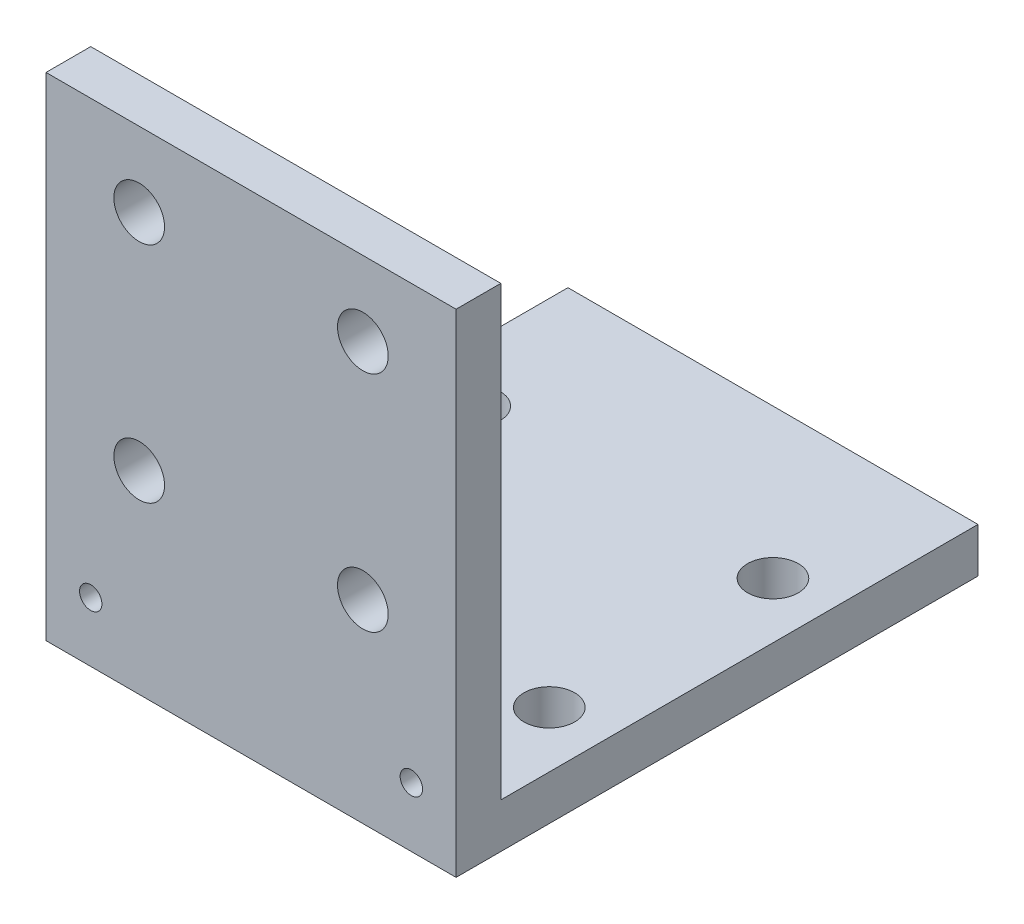
SolidWorks part; units mm, degrees
ref_plane "Front Plane" through (0, 0, 0) normal (0, 0, 1) x (1, 0, 0)
ref_plane "Top Plane" through (0, 0, 0) normal (0, 1, 0) x (1, 0, 0)
ref_plane "Right Plane" through (0, 0, 0) normal (1, 0, 0) x (0, 0, -1)
sketch "Sketch1" plane through (0, 0, 0) normal (0, 0, 1) x (1, 0, 0)
  line L1 (-13.75, 1.5) -> (13.75, 1.5)
  line L2 (-13.75, 1.5) -> (-13.75, -1.5)
  line L3 (-13.75, -1.5) -> (13.75, -1.5)
  line L4 (13.75, 1.5) -> (13.75, -1.5)
  line L5 (-13.75, 1.5) -> (13.75, -1.5) construction
  line L6 (-13.75, -1.5) -> (13.75, 1.5) construction
  point P0 (0, 0)
  dimension "D1" = 27.5
  dimension "D2" = 3
extrude "Boss-Extrude1" add sketch "Sketch1" along normal blind 35
sketch "Sketch2" plane through (0, 1.5, 0) normal (0, 1, 0) x (1, 0, 0)
  line L0 (-13.75, -32) -> (13.75, -32)
  line L1 (-13.75, -35) -> (-13.75, 0) construction
  line L2 (13.75, -35) -> (13.75, 0) construction
  line L3 (13.75, -35) -> (-13.75, -35) construction
  line L4 (13.75, -35) -> (-13.75, -35)
  line L5 (13.75, -35) -> (13.75, 0)
  line L6 (-13.75, -35) -> (-13.75, 0)
  line M3 (-13.75, 0) -> (-13.75, -35)
  line M4 (-13.75, -35) -> (13.75, -35)
  line M5 (13.75, -35) -> (13.75, 0)
  dimension "D1" = 3
extrude "Boss-Extrude2" add sketch "Sketch2" along normal blind 40 contours L0 M3 M4 M5 region at (0, 1.5, 33.5)
sketch "Sketch3" plane through (0, 1.5, 0) normal (0, 1, 0) x (1, 0, 0)
  line L0 (13.75, -35) -> (13.75, 0) construction
  line L1 (13.75, -35) -> (13.75, 0)
  line L6 (-13.75, 0) -> (-13.75, -32)
  line L7 (-13.75, -32) -> (13.75, -32)
  line L8 (13.75, -32) -> (13.75, 0)
  line L9 (13.75, 0) -> (-13.75, 0)
  line L10 (-13.75, 0) -> (-13.75, -32)
  line L11 (-13.75, -32) -> (13.75, -32)
  line L12 (13.75, -32) -> (13.75, 0)
  line L13 (13.75, 0) -> (-13.75, 0)
  circle A0 centre (10, -25) radius 1.7
  circle A1 centre (10, -10) radius 1.7
  circle A2 centre (-10, -10) radius 1.7
  circle A3 centre (-10, -25) radius 1.7
  point P8 (0, -17.5)
  point P11 (0, -17.5)
  dimension "D1" = 0
hole_wizard "M3 Clearance Hole1" positions "Sketch4" profile "Sketch5" hole size "M3" standard "ISO"
sketch "Sketch4" plane through (0, 1.5, 0) normal (0, 1, 0) x (1, 0, 0)
  point P0 (-10, -10)
  point P3 (-10, -25)
  point P6 (10, -25)
  point P9 (10, -10)
sketch "Sketch5" plane through (-10, 1.5, 10) normal (1, 0, 0) x (0, 0, 1)
  line L0 (0, 0) -> (0, 6.0215)
  line L1 (0, 6.0215) -> (1.7, 5)
  line L2 (1.7, 5) -> (1.7, 0)
  line L5 (1.7, 0) -> (0, 0)
  line L10 (0, 6.0215) -> (-1.7, 5) construction
  line L11 (0, -6.35) -> (0, 107.95) construction
  dimension "Hole Dia." = 3.4
  dimension "Hole Depth" = 5
  dimension "Drill Angle" = 118
sketch "Sketch6" plane through (0, 0, 35) normal (0, 0, 1) x (1, 0, 0)
  line L0 (-13.75, 41.5) -> (-13.75, -1.5) construction
  line L1 (-13.75, -1.5) -> (13.75, -1.5) construction
  circle A0 centre (-10.75, 2.5) radius 0.75
  dimension "D1" = 1.5
  dimension "D2" = 3
  dimension "D3" = 4
extrude "Cut-Extrude1" cut sketch "Sketch6" against normal blind 10
hole_wizard "M3 Clearance Hole2" positions "Sketch9" profile "Sketch10" hole size "M3" standard "ISO"
sketch "Sketch9" plane through (0, 0, 32) normal (0, 0, -1) x (-1, 0, 0)
  line L0 (13.75, 1.5) -> (-13.75, 1.5) construction
  point P0 (-7.5, 11.5)
  point P2 (7.5, 11.5)
  point P4 (7.5, 26.5)
  point P6 (-7.5, 26.5)
  point P17 (0, 1.5)
  dimension "D1" = 15
  dimension "D2" = 15
  dimension "D3" = 7.5
  dimension "D4" = 7.5
  dimension "D5" = 7.5
  dimension "D6" = 7.5
  dimension "D7" = 10
  dimension "D8" = 10
sketch "Sketch10" plane through (7.5, 11.5, 32) normal (1, 0, 0) x (0, 1, 0)
  line L0 (0, 0) -> (0, 6.0215)
  line L1 (0, 6.0215) -> (1.7, 5)
  line L2 (1.7, 5) -> (1.7, 0)
  line L5 (1.7, 0) -> (0, 0)
  line L10 (0, 6.0215) -> (-1.7, 5) construction
  line L11 (0, -6.35) -> (0, 107.95) construction
  dimension "Hole Dia." = 3.4
  dimension "Hole Depth" = 5
  dimension "Drill Angle" = 118
sketch "Sketch11" plane through (0, 0, 35) normal (0, 0, 1) x (1, 0, 0)
  line L4 (13.75, -1.5) -> (13.75, 41.5)
  line L5 (13.75, 41.5) -> (-13.75, 41.5)
  line L6 (-13.75, 41.5) -> (-13.75, -1.5)
  line L7 (-13.75, -1.5) -> (13.75, -1.5)
  line L8 (13.75, -1.5) -> (13.75, 41.5)
  line L9 (13.75, 41.5) -> (-13.75, 41.5)
  line L10 (-13.75, 41.5) -> (-13.75, -1.5)
  line L11 (-13.75, -1.5) -> (13.75, -1.5)
  circle A0 centre (7.5, 11.5) radius 1.7 construction
  circle A1 centre (7.5, 26.5) radius 1.7 construction
  circle A2 centre (-7.5, 26.5) radius 1.7 construction
  circle A3 centre (-7.5, 11.5) radius 1.7 construction
  circle A4 centre (7.5, 11.5) radius 1.7
  circle A5 centre (7.5, 26.5) radius 1.7
  circle A6 centre (-7.5, 26.5) radius 1.7
  circle A7 centre (-7.5, 11.5) radius 1.7
  dimension "D1" = 0
mirror "Mirror1" about plane through (0, 0, 0) normal (1, 0, 0) of "Cut-Extrude1"
sketch "Sketch12" plane through (0, 0, 32) normal (0, 0, -1) x (-1, 0, 0)
  line L0 (-13.75, 31.5) -> (13.75, 31.5)
  line L1 (-13.75, 41.5) -> (-13.75, 1.5) construction
  line L2 (13.75, 41.5) -> (13.75, 1.5) construction
  line L3 (13.75, 1.5) -> (-13.75, 1.5) construction
  line L8 (-13.75, 1.5) -> (13.75, 1.5)
  line L9 (13.75, 1.5) -> (13.75, 41.5)
  line L10 (13.75, 41.5) -> (-13.75, 41.5)
  line L11 (-13.75, 41.5) -> (-13.75, 1.5)
  line L12 (-13.75, 1.5) -> (13.75, 1.5)
  line L13 (13.75, 1.5) -> (13.75, 41.5)
  line L14 (13.75, 41.5) -> (-13.75, 41.5)
  line L15 (-13.75, 41.5) -> (-13.75, 1.5)
  line M9 (13.75, 1.5) -> (13.75, 41.5)
  line M10 (13.75, 41.5) -> (-13.75, 41.5)
  line M11 (-13.75, 41.5) -> (-13.75, 1.5)
  dimension "D1" = 30
  dimension "D2" = 0
extrude "Cut-Extrude2" cut sketch "Sketch12" against normal through all contours L0 M11 M9 M10 region at (0, 36.5, 32)
